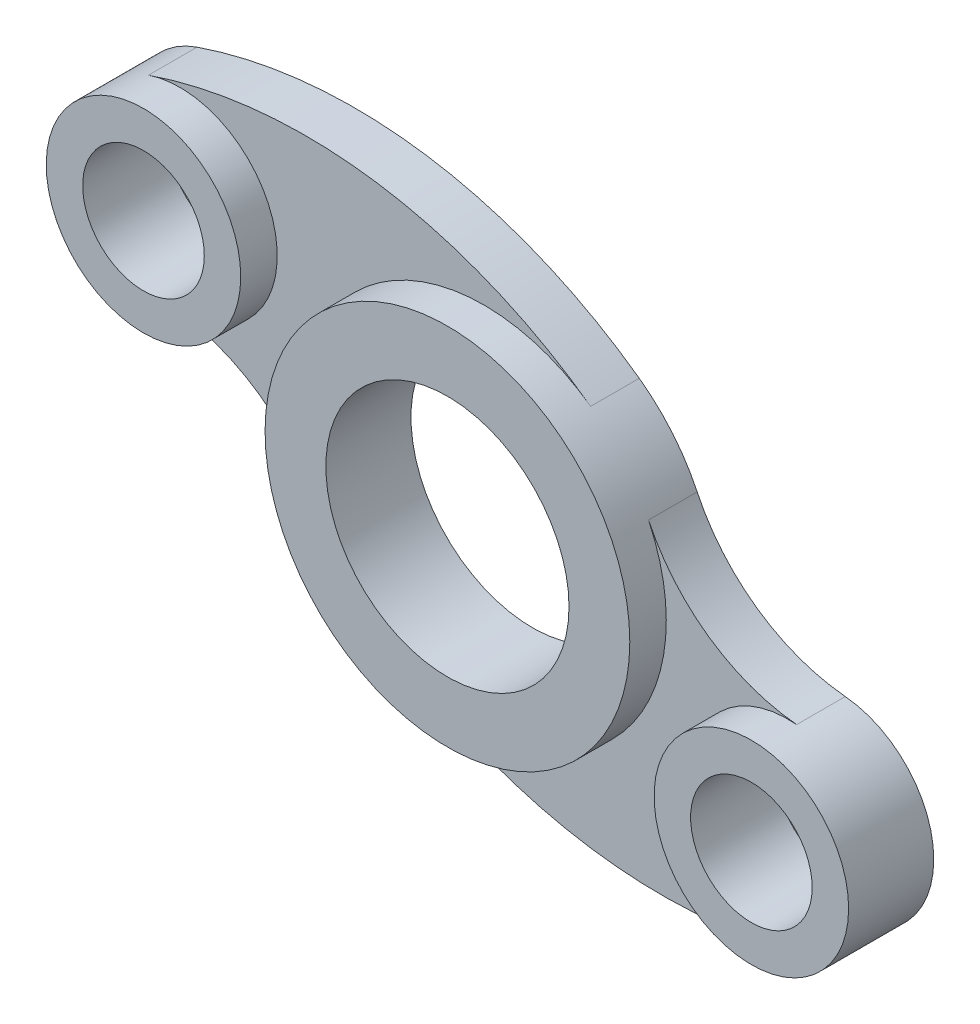
SolidWorks part; units mm, degrees
ref_plane "Piano frontale" through (0, 0, 0) normal (0, 0, 1) x (1, 0, 0)
ref_plane "Piano superiore" through (0, 0, 0) normal (0, 1, 0) x (1, 0, 0)
ref_plane "Piano destro" through (0, 0, 0) normal (1, 0, 0) x (0, 0, -1)
sketch "Schizzo1" plane through (0, 0, 0) normal (0, 0, 1) x (1, 0, 0)
  line L0 (0, 57.7789) -> (0, -49.9609) construction
  line L1 (-94.3921, 0) -> (85.8738, 0) construction
  line L2 (50, 0) -> (50, -31.6761) construction
  line L3 (28.2273, -20) -> (71.7727, -20) construction
  line L4 (-83.1984, 20) -> (-34.2257, 20) construction
  line L5 (-50, 46.1056) -> (-50, 0) construction
  circle A0 centre (0, 0) radius 30
  circle A1 centre (0, 0) radius 20
  circle A2 centre (50, -20) radius 10
  circle A3 centre (50, -20) radius 16
  circle A4 centre (-50, 20) radius 16
  circle A5 centre (-50, 20) radius 10
  arc A6 (-55.1854, 35.1364) -> (17.555, 24.3274) centre (-29.2583, -40.5457) cw
  arc A7 (51.4485, -4.0657) -> (27.0822, 12.9056) centre (54.1644, 25.8111) cw
  arc A8 (55.1854, -35.1364) -> (-17.555, -24.3274) centre (29.2583, 40.5457) cw
  arc A10 (-51.4485, 4.0657) -> (-27.0822, -12.9056) centre (-54.1644, -25.8111) cw
  point P28 (0, 0)
  point P29 (0, 0)
  point P30 (0, 0)
  point P34 (0, 0)
  point P35 (0, 0)
  dimension "D5" = 20
  dimension "D6" = 32
  dimension "D7" = 32
  dimension "D8" = 20
  dimension "D9" = 40
  dimension "D10" = 60
  dimension "D11" = 80
  dimension "D12" = 80
  dimension "D13" = 30
  dimension "D14" = 30
  dimension "D1" = 20
  dimension "D2" = 20
  dimension "D3" = 50
  dimension "D4" = 50
extrude "Estrusione-Estrusione1" add sketch "Schizzo1" along normal blind 14 contours A4 A5 | A0 A1 | A3 A2 region at (13.2765, -25.9527, 0) region at (61.4806, -9.5157, 0) region at (-40.9617, 32.6504, 0)
extrude "Estrusione-Estrusione2" add sketch "Schizzo1<3>" along normal blind 8 contours A4 A10 A0 A6 | A8 A3 A7 A0 region at (26.1262, -23.9298, 0) region at (-26.1262, 23.9298, 0)
sketch "Schizzo1<3>" plane through (0, 0, 0) normal (0, 0, 1) x (1, 0, 0) same geometry as "Schizzo1"
